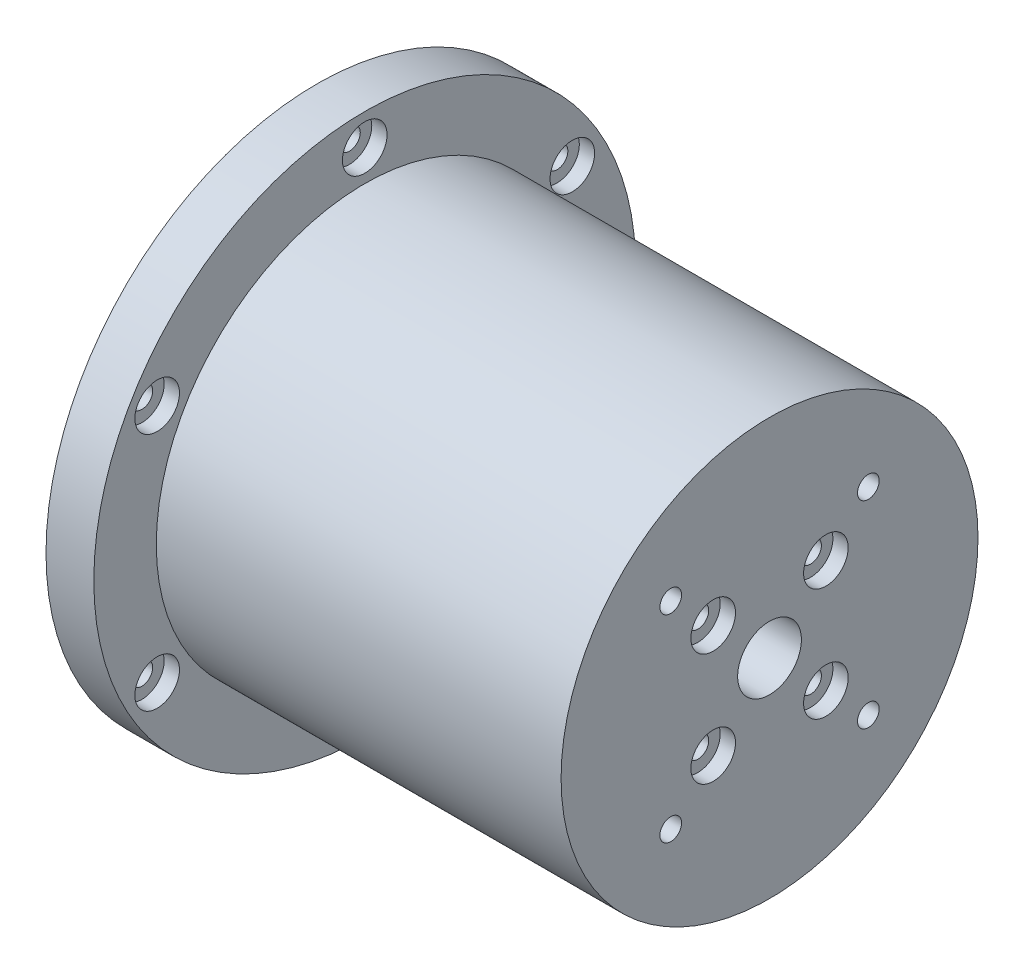
SolidWorks part; units mm, degrees
material "ABS"
ref_plane "Front" through (0, 0, 0) normal (0, 0, 1) x (1, 0, 0)
ref_plane "Top" through (0, 0, 0) normal (0, 1, 0) x (1, 0, 0)
ref_plane "Right" through (0, 0, 0) normal (1, 0, 0) x (0, 0, -1)
sketch "Croquis1" plane through (0, 0, 0) normal (1, 0, 0) x (0, 0, -1)
  circle A0 centre (0, 0) radius 32.7
  circle A1 centre (0, 0) radius 5
  dimension "D1" = 65.4
  dimension "D2" = 10
extrude "Saliente-Extruir1" add sketch "Croquis1" along normal mid plane 8.5
hole_wizard "Refrentado para tornillo con cabeza troncocónica de M31" positions "Croquis2" profile "Croquis4" counterbore size "M3" standard "Ansi Metric" end condition up to next
sketch "Croquis2" plane through (4.25, 0, 0) normal (1, 0, 0) x (0, 0, -1)
  line L1 (-8.8388, -8.8388) -> (8.8388, -8.8388) construction
  line L2 (-8.8388, -8.8388) -> (-8.8388, 8.8388) construction
  line L3 (-8.8388, 8.8388) -> (8.8388, 8.8388) construction
  line L4 (8.8388, -8.8388) -> (8.8388, 8.8388) construction
  line L5 (-8.8388, -8.8388) -> (8.8388, 8.8388) construction
  line L6 (-8.8388, 8.8388) -> (8.8388, -8.8388) construction
  point P2 (8.8388, 8.8388)
  point P25 (-8.8388, -8.8388)
  point P26 (-8.8388, 8.8388)
  point P27 (8.8388, -8.8388)
  dimension "D1" = 25
sketch "Croquis4" plane through (4.25, 8.8388, -8.8388) normal (0, 1, 0) x (0, 0, -1)
  line L0 (0, 0) -> (0, 8.5)
  line L1 (0, 8.5) -> (1.7, 8.5)
  line L3 (1.7, 8.5) -> (1.7, 2.4)
  line L4 (1.7, 2.4) -> (3.5, 2.4)
  line L5 (3.5, 2.4) -> (3.5, 0)
  line L7 (3.5, 0) -> (0, 0)
  line L11 (0, -6.35) -> (0, 107.95) construction
  dimension "Diámetro de taladro hasta el siguiente" = 3.4
  dimension "Profundidad de taladro hasta el siguiente" = 8.5
  dimension "Diámetro de refrentado" = 7
  dimension "Profundidad de refrentado" = 2.4
sketch "Croquis5" plane through (-4.25, 0, 0) normal (-1, 0, 0) x (0, 0, 1)
  circle A0 centre (0, 0) radius 21.5
  circle A1 centre (0, 0) radius 32.7 construction
  circle A2 centre (0, 0) radius 32.7
  dimension "D1" = 43
extrude "Saliente-Extruir2" add sketch "Croquis5" along normal blind 55
hole_wizard "Taladro de margen para M31" positions "Croquis6" profile "Croquis8" hole size "M3" standard "Ansi Metric"
sketch "Croquis6" plane through (-59.25, 0, 0) normal (-1, 0, 0) x (0, 0, 1)
  line L1 (-17.075, -17.075) -> (17.075, -17.075) construction
  line L2 (-17.075, -17.075) -> (-17.075, 17.075) construction
  line L3 (-17.075, 17.075) -> (17.075, 17.075) construction
  line L4 (17.075, -17.075) -> (17.075, 17.075) construction
  line L5 (-17.075, -17.075) -> (17.075, 17.075) construction
  line L6 (-17.075, 17.075) -> (17.075, -17.075) construction
  point P2 (17.075, 17.075)
  point P25 (-17.075, -17.075)
  point P26 (-17.075, 17.075)
  point P27 (17.075, -17.075)
  dimension "D1" = 34.15
sketch "Croquis8" plane through (-59.25, 17.075, 17.075) normal (0, 1, 0) x (0, 0, 1)
  line L0 (0, 0) -> (0, 16.0215)
  line L1 (0, 16.0215) -> (1.7, 15)
  line L2 (1.7, 15) -> (1.7, 0)
  line L5 (1.7, 0) -> (0, 0)
  line L10 (0, 16.0215) -> (-1.7, 15) construction
  line L11 (0, -6.35) -> (0, 107.95) construction
  dimension "Diámetro de taladro" = 3.4
  dimension "Profundidad de taladro" = 15
  dimension "Ángulo de perforador" = 118
hole_wizard "Taladro de margen para M32" positions "Croquis9" profile "Croquis10" hole size "M3" standard "Ansi Metric"
sketch "Croquis9" plane through (4.25, 0, 0) normal (1, 0, 0) x (0, 0, -1)
  line L1 (-15.5, -15.5) -> (15.5, -15.5) construction
  line L2 (-15.5, -15.5) -> (-15.5, 15.5) construction
  line L3 (-15.5, 15.5) -> (15.5, 15.5) construction
  line L4 (15.5, -15.5) -> (15.5, 15.5) construction
  line L5 (-15.5, -15.5) -> (15.5, 15.5) construction
  line L6 (-15.5, 15.5) -> (15.5, -15.5) construction
  point P2 (15.5, 15.5)
  point P13 (-15.5, -15.5)
  point P14 (-15.5, 15.5)
  point P15 (15.5, -15.5)
  dimension "D1" = 31
sketch "Croquis10" plane through (4.25, 15.5, -15.5) normal (0, 1, 0) x (0, 0, -1)
  line L0 (0, 0) -> (0, 17.5215)
  line L1 (0, 17.5215) -> (1.7, 16.5)
  line L2 (1.7, 16.5) -> (1.7, 0)
  line L5 (1.7, 0) -> (0, 0)
  line L10 (0, 17.5215) -> (-1.7, 16.5) construction
  line L11 (0, -6.35) -> (0, 107.95) construction
  dimension "Diámetro de taladro" = 3.4
  dimension "Profundidad de taladro" = 16.5
  dimension "Ángulo de perforador" = 118
sketch "Croquis12" plane through (-4.25, 0, 0) normal (-1, 0, 0) x (0, 0, 1)
  line L0 (-15.5, 15.5) -> (0, 0) construction
  line L1 (-13.2514, 13.2514) -> (-12.4284, 16.323)
  line L2 (-12.4284, 16.323) -> (-14.677, 18.5716)
  line L3 (-14.677, 18.5716) -> (-17.7486, 17.7486)
  line L4 (-17.7486, 17.7486) -> (-18.5716, 14.677)
  line L5 (-18.5716, 14.677) -> (-16.323, 12.4284)
  line L6 (-16.323, 12.4284) -> (-13.2514, 13.2514)
  line L7 (13.2514, 13.2514) -> (16.323, 12.4284)
  line L8 (16.323, 12.4284) -> (18.5716, 14.677)
  line L9 (18.5716, 14.677) -> (17.7486, 17.7486)
  line L10 (17.7486, 17.7486) -> (14.677, 18.5716)
  line L11 (14.677, 18.5716) -> (12.4284, 16.323)
  line L12 (12.4284, 16.323) -> (13.2514, 13.2514)
  line L13 (13.2514, -13.2514) -> (12.4284, -16.323)
  line L14 (12.4284, -16.323) -> (14.677, -18.5716)
  line L15 (14.677, -18.5716) -> (17.7486, -17.7486)
  line L16 (17.7486, -17.7486) -> (18.5716, -14.677)
  line L17 (18.5716, -14.677) -> (16.323, -12.4284)
  line L18 (16.323, -12.4284) -> (13.2514, -13.2514)
  line L19 (-13.2514, -13.2514) -> (-16.323, -12.4284)
  line L20 (-16.323, -12.4284) -> (-18.5716, -14.677)
  line L21 (-18.5716, -14.677) -> (-17.7486, -17.7486)
  line L22 (-17.7486, -17.7486) -> (-14.677, -18.5716)
  line L23 (-14.677, -18.5716) -> (-12.4284, -16.323)
  line L24 (-12.4284, -16.323) -> (-13.2514, -13.2514)
  circle A0 centre (-15.5, 15.5) radius 2.754 construction
  circle A1 centre (15.5, 15.5) radius 2.754 construction
  circle A2 centre (15.5, -15.5) radius 2.754 construction
  circle A3 centre (-15.5, -15.5) radius 2.754 construction
  dimension "D1" = 3.18
  dimension "D2" = 4
extrude "Cortar-Extruir1" cut sketch "Croquis12" along normal blind 4
sketch "Croquis16" plane through (-59.25, 0, 0) normal (-1, 0, 0) x (0, 0, 1)
  line L0 (17.8486, 21.5) -> (21.5986, 17.75)
  line L1 (-21.3999, -21.4985) -> (21.5986, -21.4985) construction
  line L2 (-21.3999, -21.4985) -> (-21.3999, 21.5) construction
  line L3 (-21.3999, 21.5) -> (21.5986, 21.5) construction
  line L4 (21.5986, -21.4985) -> (21.5986, 21.5) construction
  line L5 (-21.3999, -21.4985) -> (21.5986, 21.5) construction
  line L6 (-21.3999, 21.5) -> (21.5986, -21.4985) construction
  line L7 (21.5986, 17.75) -> (21.5986, -17.7485)
  line L8 (21.5986, -17.7485) -> (17.8486, -21.4985)
  line L9 (17.8486, -21.4985) -> (-17.6499, -21.4985)
  line L10 (-17.6499, -21.4985) -> (-21.3999, -17.7485)
  line L11 (-21.3999, -17.7485) -> (-21.3999, 17.75)
  line L12 (-21.3999, 17.75) -> (-17.6499, 21.5)
  line L13 (-17.6499, 21.5) -> (17.8486, 21.5)
  circle A0 centre (0, 0) radius 21.5 construction
  circle A1 centre (0, 0) radius 42.5
  point P4 (0, 0)
  dimension "D1" = 85
  dimension "D2" = 3.75
  dimension "D3" = 3.75
extrude "Saliente-Extruir3" add sketch "Croquis16" along normal blind 7.5
hole_wizard "Refrentado para tornillo con cabeza troncocónica de M32" positions "Croquis20" profile "Croquis21" counterbore size "M3" standard "Ansi Metric" end condition up to next
sketch "Croquis20" plane through (-59.25, 0, 0) normal (1, 0, 0) x (0, 0, -1)
  line L0 (0, 42.5) -> (0, 32.7) construction
  line L1 (0, 39.05) -> (0, -39.05) construction
  circle A0 centre (0, 0) radius 42.5 construction
  circle A1 centre (0, 0) radius 32.7 construction
  point P14 (0, 37.6)
  point P21 (32.5626, 18.8)
  point P22 (32.5626, -18.8)
  point P23 (0, -37.6)
  point P24 (-32.5626, -18.8)
  point P25 (-32.5626, 18.8)
  dimension "D1" = 6
sketch "Croquis21" plane through (-59.25, 18.8, 32.5626) normal (0, 1, 0) x (0, 0, -1)
  line L0 (0, 0) -> (0, 7.5)
  line L1 (0, 7.5) -> (1.7, 7.5)
  line L3 (1.7, 7.5) -> (1.7, 2.4)
  line L4 (1.7, 2.4) -> (3.5, 2.4)
  line L5 (3.5, 2.4) -> (3.5, 0)
  line L7 (3.5, 0) -> (0, 0)
  line L11 (0, -6.35) -> (0, 107.95) construction
  dimension "Diámetro de taladro hasta el siguiente" = 3.4
  dimension "Profundidad de taladro hasta el siguiente" = 7.5
  dimension "Diámetro de refrentado" = 7
  dimension "Profundidad de refrentado" = 2.4
